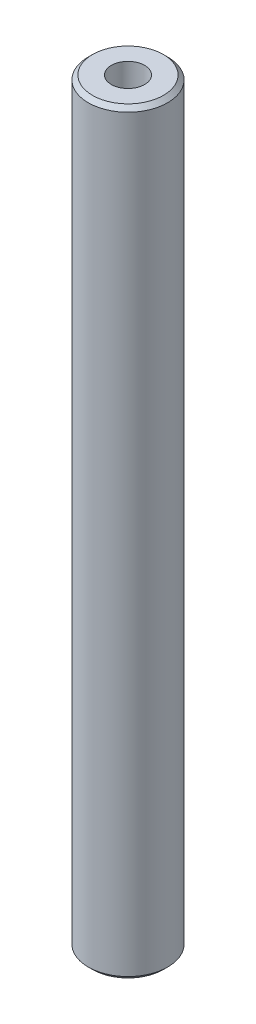
SolidWorks part; units mm, degrees
ref_plane "Front Plane" through (0, 0, 0) normal (0, 0, 1) x (1, 0, 0)
ref_plane "Top Plane" through (0, 0, 0) normal (0, 1, 0) x (1, 0, 0)
ref_plane "Right Plane" through (0, 0, 0) normal (1, 0, 0) x (0, 0, -1)
sketch "Sketch1" plane through (0, 0, 0) normal (0, 1, 0) x (1, 0, 0)
  circle A0 centre (0, 0) radius 10
  dimension "SHAFT_OD" = 20
extrude "Boss-Extrude1" add sketch "Sketch1" along normal blind 190.7077
sketch "Sketch2" plane through (0, 0, 0) normal (0, 1, 0) x (1, 0, 0)
  circle A0 centre (0, 0) radius 4.1932
  dimension "BORE_D" = 8.3865
extrude "Cut-Extrude1" cut sketch "Sketch2" along normal through all
chamfer "Chamfer1" distance 1.0703 angle 45 2 edges at (0, 190.7077, 10) (0, 0, 10)
